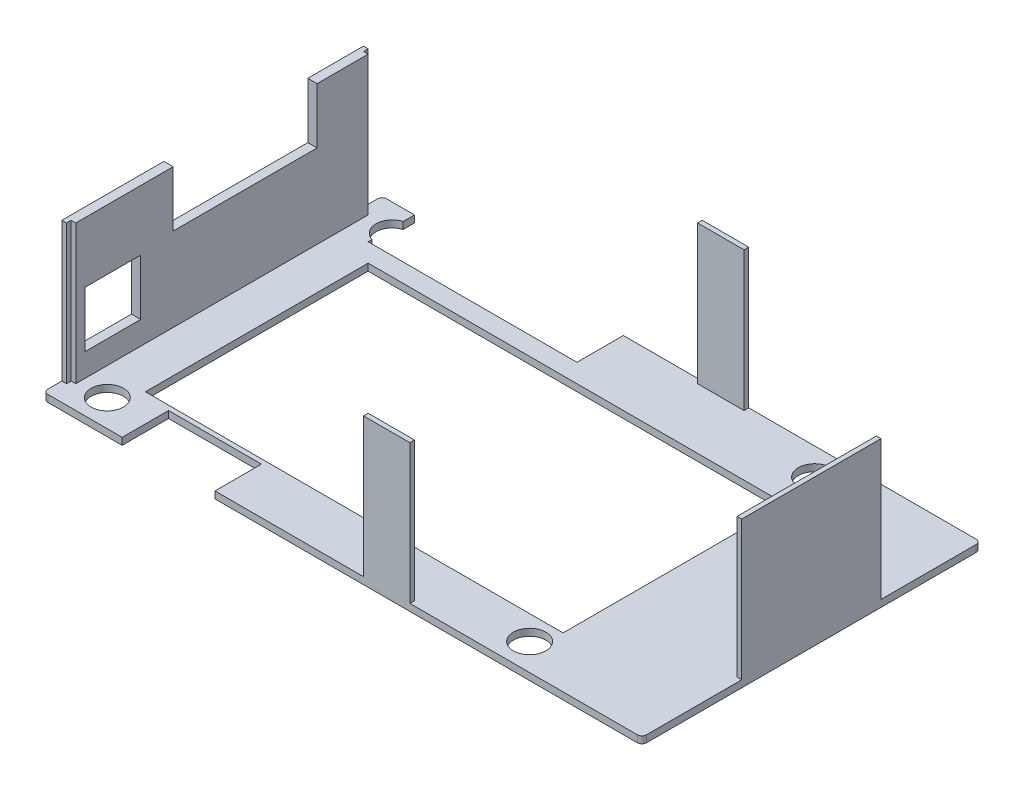
SolidWorks part; units mm, degrees
ref_plane "前视基准面" through (0, 0, 0) normal (0, 0, 1) x (1, 0, 0)
ref_plane "上视基准面" through (0, 0, 0) normal (0, 1, 0) x (1, 0, 0)
ref_plane "右视基准面" through (0, 0, 0) normal (1, 0, 0) x (0, 0, -1)
other "Configuration Table"
sketch "草图1" plane through (0, 0, 0) normal (0, 1, 0) x (1, 0, 0)
  line L0 (-64.5, 0) -> (-84.5, 0) construction
  line L1 (-64.5, 36.5) -> (64.5, 36.5)
  line L2 (-64.5, 36.5) -> (-64.5, -36.5)
  line L3 (-64.5, -36.5) -> (64.5, -36.5)
  line L4 (64.5, 36.5) -> (64.5, -36.5)
  line L5 (0, -36.5) -> (0, -56.5) construction
  line L7 (-64.5, 31.5) -> (-62.5, 31.5)
  line L8 (-64.5, 31.5) -> (-64.5, -31.5)
  line L9 (-64.5, -31.5) -> (-62.5, -31.5)
  line L10 (-62.5, 31.5) -> (-62.5, -31.5)
  line L11 (-64.5, 31.5) -> (-63.5, 31.5)
  line L12 (-64.5, 31.5) -> (-64.5, 32.5)
  line L13 (-64.5, 32.5) -> (-63.5, 32.5)
  line L14 (-63.5, 31.5) -> (-63.5, 32.5)
  line L15 (-64.5, -31.5) -> (-63.5, -31.5)
  line L16 (-64.5, -31.5) -> (-64.5, -32.5)
  line L17 (-64.5, -32.5) -> (-63.5, -32.5)
  line L18 (-63.5, -31.5) -> (-63.5, -32.5)
  dimension "D1" = 73
  dimension "D2" = 129
  dimension "D3" = 20
  dimension "D4" = 20
  dimension "D5" = 2
  dimension "D6" = 5
  dimension "D7" = 5
  dimension "D8" = 1
  dimension "D9" = 1
  dimension "D10" = 1
  dimension "D11" = 1
extrude "凸台-拉伸1" add sketch "草图1" along normal blind 30 contours L18 L9 L2 L17 | L10 L7 L2 L9 | L7 L14 L13 L2 region at (-64, 0, -32) region at (-63.5, 0, 0) region at (-64, 0, 32)
extrude "凸台-拉伸3" add sketch "草图1<5>" against normal blind 1.5 contours L2 L3 L4 L1
sketch "草图1<5>" plane through (0, 0, 0) normal (0, 1, 0) x (1, 0, 0) same geometry as "草图1"
sketch "草图4" plane through (0, 0, 0) normal (0, 1, 0) x (1, 0, 0)
  line L0 (0, 0) -> (90, 0) construction
  line L1 (64.5, 36.5) -> (64.5, -36.5) construction
  line L2 (64.5, 15) -> (63.5, 15)
  line L3 (64.5, 15) -> (64.5, -15)
  line L4 (64.5, -15) -> (63.5, -15)
  line L5 (63.5, 15) -> (63.5, -15)
  line L6 (-64.5, -36.5) -> (64.5, -36.5) construction
  line L7 (14.5, -36.5) -> (4.5, -36.5)
  line L8 (14.5, -36.5) -> (14.5, -35.5)
  line L9 (14.5, -35.5) -> (4.5, -35.5)
  line L10 (4.5, -36.5) -> (4.5, -35.5)
  line L11 (4.5, 36.5) -> (4.5, 35.5)
  line L12 (14.5, 35.5) -> (4.5, 35.5)
  line L13 (14.5, 36.5) -> (14.5, 35.5)
  line L14 (14.5, 36.5) -> (4.5, 36.5)
  dimension "D1" = 90
  dimension "D2" = 1
  dimension "D3" = 15
  dimension "D4" = 30
  dimension "D5" = 60
  dimension "D6" = 10
  dimension "D7" = 1
extrude "凸台-拉伸4" add sketch "草图4" along normal blind 30
sketch "草图6" plane through (0, -1.5, 0) normal (0, -1, 0) x (1, 0, 0)
  line L0 (64.5, -36.5) -> (64.5, 36.5) construction
  line L1 (-53.5, 25.5) -> (36.5, 25.5)
  line L2 (-53.5, 25.5) -> (-53.5, -22.5)
  line L3 (-53.5, -22.5) -> (36.5, -22.5)
  line L4 (36.5, 25.5) -> (36.5, -22.5)
  line L5 (-64.5, 36.5) -> (64.5, 36.5) construction
  line L6 (-64.5, -36.5) -> (64.5, -36.5) construction
  line L7 (0, 0) -> (-70, 0) construction
  line L17 (-47.5, 36.5) -> (-27.5, 36.5)
  line L18 (-27.5, 26.5) -> (-27.5, 36.5)
  line L19 (-47.5, 26.5) -> (-27.5, 26.5)
  line L20 (-47.5, 26.5) -> (-47.5, 36.5)
  line L21 (-57.5, -36.5) -> (-12.5, -36.5)
  line L22 (-12.5, -26.5) -> (-12.5, -36.5)
  line L23 (-57.5, -26.5) -> (-12.5, -26.5)
  line L24 (-57.5, -26.5) -> (-57.5, -36.5)
  line L25 (-64.5, -36.5) -> (-64.5, 36.5) construction
  dimension "D1" = 48
  dimension "D2" = 90
  dimension "D3" = 28
  dimension "D4" = 11
  dimension "D5" = 7
  dimension "D6" = 52
  dimension "D7" = 10
  dimension "D8" = 10
  dimension "D9" = 17
  dimension "D10" = 37
  dimension "D11" = 70
sketch "草图8" plane through (-64.5, 0, 0) normal (-1, 0, 0) x (0, 0, 1)
  line L0 (-32.5, 30) -> (32.5, 30) construction
  line L1 (-32.5, 30) -> (-32.5, 0) construction
  line L2 (10.5, 30) -> (-20.5, 30)
  line L3 (10.5, 30) -> (10.5, 18)
  line L4 (10.5, 18) -> (-20.5, 18)
  line L5 (-20.5, 30) -> (-20.5, 18)
  line L6 (32.5, 30) -> (32.5, 0) construction
  line L8 (17.5, 17) -> (29.5, 17)
  line L9 (17.5, 17) -> (17.5, 5)
  line L10 (17.5, 5) -> (29.5, 5)
  line L11 (29.5, 17) -> (29.5, 5)
  dimension "D1" = 12
  dimension "D2" = 22
  dimension "D3" = 12
  dimension "D4" = 12
  dimension "D5" = 50
  dimension "D6" = 13
  dimension "D7" = 12
extrude "切除-拉伸5" cut sketch "草图8" against normal blind 2
extrude "切除-拉伸6" cut sketch "草图6" against normal blind 2
fillet "圆角1" radius 1 1 edges at (-64.5, -0.75, -36.5)
fillet "圆角6" radius 1 1 edges at (-64.5, -0.75, 36.5)
fillet "圆角7" radius 1 2 edges at (64.5, -0.75, -36.5) (64.5, -0.75, 36.5)
sketch "草图10" plane through (0, -1.5, 0) normal (0, -1, 0) x (-1, 0, 0)
  line L0 (-64.5, 35.5) -> (-64.5, -35.5) construction
  line L1 (12.5, 36.5) -> (-63.5, 36.5) construction
  line L2 (57.5, 27.3459) -> (57.5, 34.0541)
  line L4 (27.5, -36.5) -> (-63.5, -36.5) construction
  circle A0 centre (-34.5, 30.7) radius 3.5
  circle A1 centre (-34.5, -30.7) radius 3.5
  circle A3 centre (56.5, -30.7) radius 3.5
  arc A4 (57.5, 27.3459) -> (57.5, 34.0541) centre (56.5, 30.7) ccw
  dimension "D1" = 7
  dimension "D4" = 5.8
  dimension "D5" = 7
  dimension "D7" = 7
  dimension "D8" = 7
  dimension "D2" = 30
  dimension "D3" = 5.8
  dimension "D6" = 91
  dimension "D9" = 6.7082
extrude "切除-拉伸7" cut sketch "草图10" against normal blind 2
